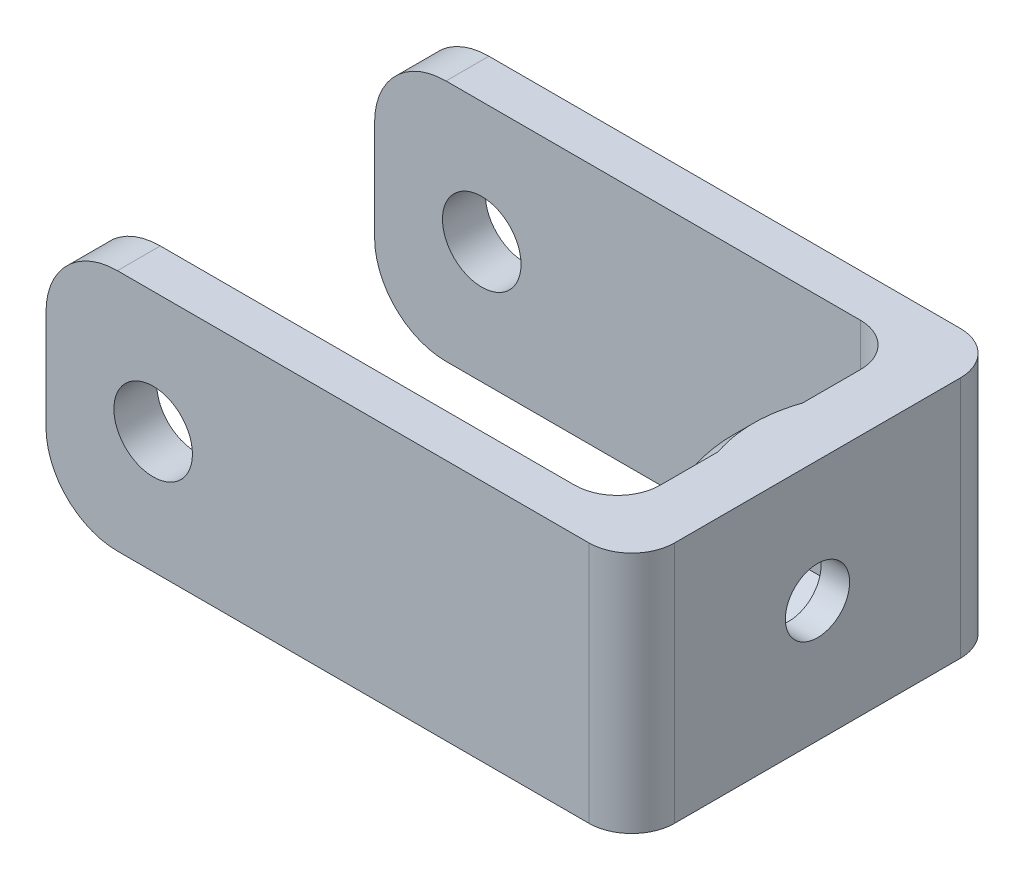
SolidWorks part; units mm, degrees
ref_plane "Front Plane" through (0, 0, 0) normal (0, 0, 1) x (1, 0, 0)
ref_plane "Top Plane" through (0, 0, 0) normal (0, 1, 0) x (1, 0, 0)
ref_plane "Right Plane" through (0, 0, 0) normal (1, 0, 0) x (0, 0, -1)
sketch "Sketch1" plane through (0, 0, 0) normal (1, 0, 0) x (0, 0, -1)
  line L1 (-13, -8.5) -> (13, -8.5)
  line L2 (-13, -8.5) -> (-13, 8.5)
  line L3 (-13, 8.5) -> (13, 8.5)
  line L4 (13, -8.5) -> (13, 8.5)
  line L5 (-13, -8.5) -> (13, 8.5) construction
  line L6 (-13, 8.5) -> (13, -8.5) construction
  point P0 (0, 0)
  dimension "D1" = 17
  dimension "D2" = 26
extrude "Boss-Extrude1" add sketch "Sketch1" along normal blind 4
sketch "Sketch2" plane through (0, 0, 0) normal (-1, 0, 0) x (0, 0, 1)
  line L0 (13, -8.5) -> (-13, -8.5) construction
  line L1 (-13, 8.5) -> (-10, 8.5)
  line L2 (-13, 8.5) -> (-13, -8.5)
  line L3 (-13, -8.5) -> (-10, -8.5)
  line L4 (-10, 8.5) -> (-10, -8.5)
  line L6 (13, 8.5) -> (10, 8.5)
  line L7 (13, 8.5) -> (13, -8.5)
  line L8 (13, -8.5) -> (10, -8.5)
  line L9 (10, 8.5) -> (10, -8.5)
  dimension "D1" = 3
  dimension "D2" = 3
extrude "Boss-Extrude2" add sketch "Sketch2" along normal blind 37
sketch "Sketch3" plane through (0, 0, 13) normal (0, 0, 1) x (1, 0, 0)
  line L1 (-37, -8.5) -> (-37, 8.5) construction
  circle A0 centre (-29.5, 0) radius 2.75
  dimension "D1" = 5.5
  dimension "D2" = 7.5
extrude "Cut-Extrude1" cut sketch "Sketch3" against normal through all
fillet "Fillet1" radius 3 4 edges at (0, 0, 10) (4, 0, 13) (4, 0, -13) (0, 0, -10)
fillet "Fillet2" radius 5 4 edges at (-37, 8.5, -11.5) (-37, -8.5, -11.5) (-37, -8.5, 11.5) (-37, 8.5, 11.5)
sketch "Sketch5" plane through (0, 0, 0) normal (-1, 0, 0) x (0, 0, 1)
  circle A0 centre (0, 0) radius 7
  dimension "D1" = 14
extrude "Boss-Extrude3" add sketch "Sketch5" along normal blind 2
sketch "Sketch7" plane through (4, 0, 0) normal (1, 0, 0) x (0, 0, -1)
  circle A0 centre (0, 0) radius 2.25
  dimension "D1" = 4.5
extrude "Cut-Extrude3" cut sketch "Sketch7" against normal up to next
sketch "Sketch8" plane through (-2, 0, 0) normal (-1, 0, 0) x (0, 0, 1)
  line L1 (0, 4.3301) -> (-3.75, 2.1651)
  line L2 (-3.75, 2.1651) -> (-3.75, -2.1651)
  line L3 (-3.75, -2.1651) -> (0, -4.3301)
  line L4 (0, -4.3301) -> (3.75, -2.1651)
  line L5 (3.75, -2.1651) -> (3.75, 2.1651)
  line L6 (3.75, 2.1651) -> (0, 4.3301)
  circle A0 centre (0, 0) radius 3.75 construction
  dimension "D1" = 7.5
extrude "Cut-Extrude4" cut sketch "Sketch8" against normal blind 4
chamfer "Chamfer1" distance 2 angle 45 2 edges at (0, 7, 0) (0, -7, 0)
